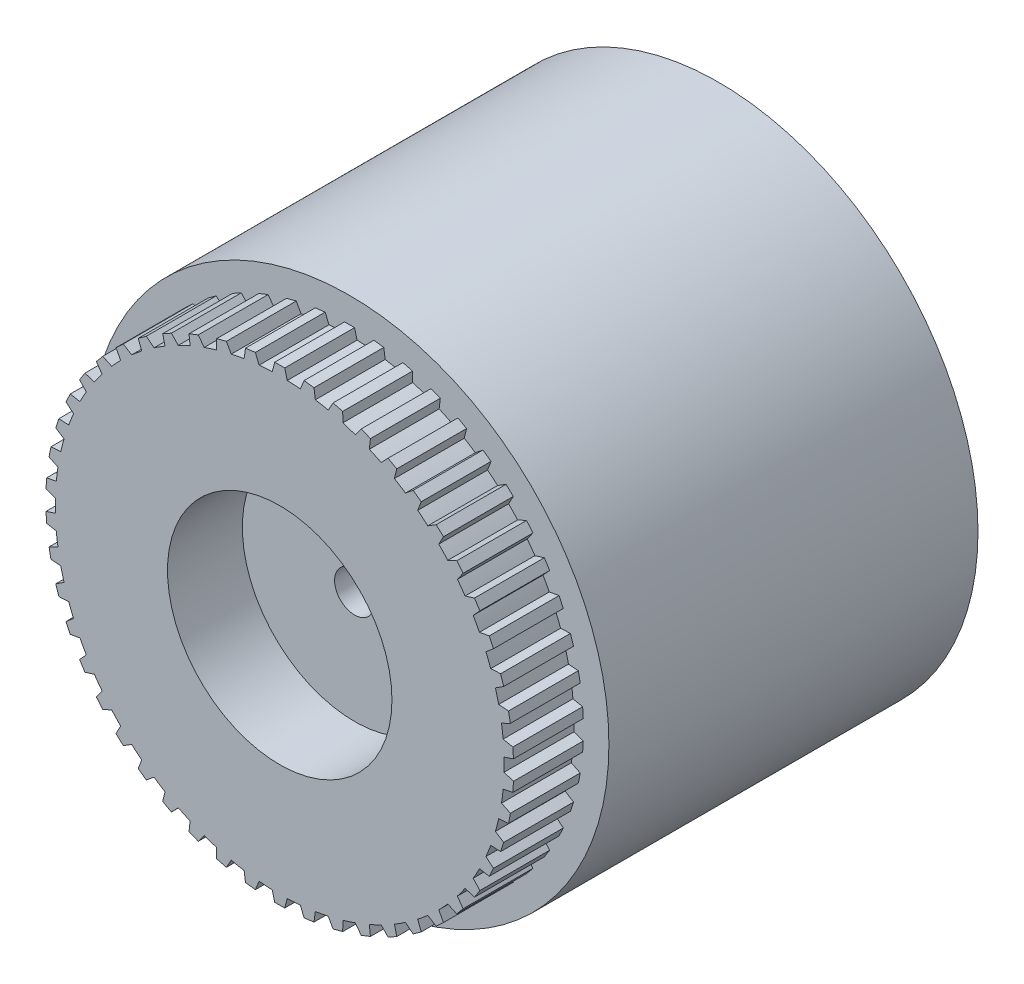
SolidWorks part; units mm, degrees
ref_plane "Front Plane" through (0, 0, 0) normal (0, 0, 1) x (1, 0, 0)
ref_plane "Top Plane" through (0, 0, 0) normal (0, 1, 0) x (1, 0, 0)
ref_plane "Right Plane" through (0, 0, 0) normal (1, 0, 0) x (0, 0, -1)
sketch "Sketch1" plane through (0, 0, 0) normal (0, 0, 1) x (1, 0, 0)
  circle A0 centre (0, 0) radius 26
  dimension "D1" = 52
extrude "Boss-Extrude1" add sketch "Sketch1" along normal blind 37
sketch "Sketch2" plane through (0, 0, 37) normal (0, 0, 1) x (1, 0, 0)
  circle A0 centre (0, 0) radius 22.5
  dimension "D1" = 45
extrude "Boss-Extrude2" add sketch "Sketch2" along normal blind 7
sketch "Sketch3" plane through (0, 0, 44) normal (0, 0, 1) x (1, 0, 0)
  line L0 (0, 0) -> (0, 23.4454) construction
  line L1 (0, 23.4454) -> (-0.5, 23.4454)
  line L2 (-0.5, 23.4454) -> (-1.7978, 18.6021)
  line L3 (0, 23.4454) -> (0.5, 23.4454)
  line L4 (0.5, 23.4454) -> (1.7978, 18.6021)
  line L5 (1.7978, 18.6021) -> (-1.7978, 18.6021)
  dimension "D1" = 0.5
  dimension "D2" = 0.5
  dimension "D3" = 75
  dimension "D4" = 75
  dimension "D5" = 23.4454
  dimension "D6" = 18.6021
extrude "Boss-Extrude3" add sketch "Sketch3" against normal blind 7
pattern_circular "CirPattern1" count 50 over 360 about axis through (0, 0, 44) along (0, 0, -1) of "Boss-Extrude3" reverse direction yes
sketch "Sketch4" plane through (0, 0, 0) normal (0, 0, -1) x (-1, 0, 0)
  circle A0 centre (0, 0) radius 6.75
  dimension "D1" = 13.5
extrude "Cut-Extrude1" cut sketch "Sketch4" against normal blind 5.5
sketch "Sketch5" plane through (0, 0, 5.5) normal (0, 0, -1) x (-1, 0, 0)
  circle A0 centre (0, 0) radius 2
  dimension "D1" = 4
extrude "Cut-Extrude2" cut sketch "Sketch5" against normal through all
sketch "Sketch6" plane through (0, 0, 44) normal (0, 0, 1) x (1, 0, 0)
  circle A0 centre (0, 0) radius 11.25
  dimension "D1" = 22.5
extrude "Cut-Extrude3" cut sketch "Sketch6" against normal blind 7.5
